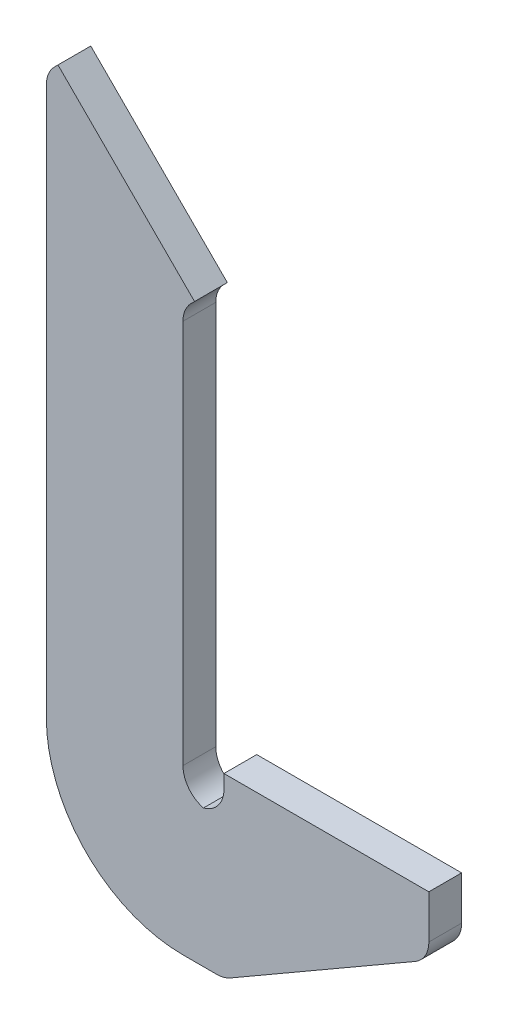
SolidWorks part; units mm, degrees
material "PBT General Purpose"
ref_plane "Front Plane" through (0, 0, 0) normal (0, 0, 1) x (1, 0, 0)
ref_plane "Top Plane" through (0, 0, 0) normal (0, 1, 0) x (1, 0, 0)
ref_plane "Right Plane" through (0, 0, 0) normal (1, 0, 0) x (0, 0, -1)
sketch "Sketch1" plane through (0, 0, 0) normal (0, 0, 1) x (1, 0, 0)
  line L0 (0, 0) -> (-1.5, 0)
  line L1 (-1.5, 0) -> (-1.5, -0.3)
  line L2 (-1.5, -0.3) -> (-1.8, -0.3)
  line L3 (-1.8, -0.3) -> (-1.8, 2.8)
  line L5 (-2.8, 3.8) -> (-2.8, -1.3)
  line L6 (-2.8, -1.3) -> (-1.5, -1.3)
  line L7 (-1.5, -1.3) -> (0, -0.434)
  line L8 (0, -0.434) -> (0, 0)
  line L9 (-1.8, 2.8) -> (-2.8, 3.8) construction
  line L10 (0, 0) -> (1, 0) construction
  line L11 (-1.8, 2.8) -> (1, 0) construction
  line L12 (-1.8, 2.8) -> (-1.7151, 2.8849)
  line L13 (-1.7151, 2.8849) -> (-2.7151, 3.8849)
  line L14 (-2.7151, 3.8849) -> (-2.8, 3.8)
  point P11 (-1.65, -0.3)
  dimension "D1" = 1.5
  dimension "D2" = 0.3
  dimension "D3" = 0.3
  dimension "D4" = 1
  dimension "D5" = 45
  dimension "D6" = 120
  dimension "D7" = 1
  dimension "D8" = 1
  dimension "D9" = 45
  dimension "D10" = 0.12
extrude "Boss-Extrude1" add sketch "Sketch1" along normal mid plane 0.24 contours L5 L6 L7 L8 L0 L1 L2 L3 L12 L13 L14
fillet "Fillet1" radius 1 1 edges at (-2.8, -1.3, 0)
fillet "Fillet2" radius 0.2 6 edges at (-1.8, 2.8, 0) (-2.8, 3.8, 0) (-1.5, -1.3, 0) (0, -0.434, 0) (-1.5, -0.3, 0) (-1.8, -0.3, 0)
